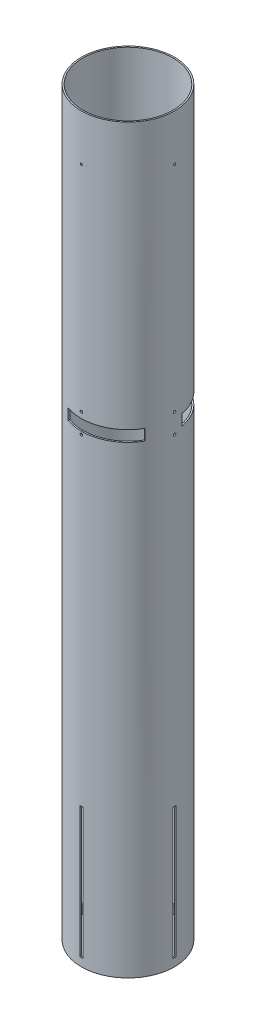
SolidWorks part; units mm, degrees
material "A-Glass Fiber"
ref_plane "Front Plane" through (0, 0, 0) normal (0, 0, 1) x (1, 0, 0)
ref_plane "Top Plane" through (0, 0, 0) normal (0, 1, 0) x (1, 0, 0)
ref_plane "Right Plane" through (0, 0, 0) normal (1, 0, 0) x (0, 0, -1)
sketch "Sketch1" plane through (0, 0, 0) normal (0, 1, 0) x (1, 0, 0)
  circle A0 centre (0, 0) radius 49.53
  circle A1 centre (0, 0) radius 51.1048
  dimension "D1" = 99.06
  dimension "D2" = 102.2096
extrude "Boss-Extrude1" add sketch "Sketch1" along normal blind 812.8
ref_plane "Plane1" through (0, 0, 0) normal (0.7071, 0, 0.7071) x (0.7071, 0, -0.7071)
ref_axis "Axis1" through (0, 812.8, 0) along (0, -1, 0)
sketch "Sketch2" plane through (0, 0, 0) normal (1, 0, 0) x (0, 0, -1)
  line L0 (0, 0) -> (0, 8.89)
  line L1 (1.5875, 8.89) -> (-1.5875, 8.89)
  line L2 (1.5875, 8.89) -> (1.5875, 152.4)
  line L3 (1.5875, 152.4) -> (-1.5875, 152.4)
  line L4 (-1.5875, 8.89) -> (-1.5875, 152.4)
  line L5 (1.5875, 8.89) -> (-1.5875, 152.4) construction
  line L6 (1.5875, 152.4) -> (-1.5875, 8.89) construction
  line L7 (51.1048, 812.8) -> (-51.1048, 812.8) construction
  line L8 (51.1048, 812.8) -> (-51.1048, 812.8)
  line L9 (0, 812.8) -> (0, 527.05)
  line L10 (-51.1048, 0) -> (51.1048, 0) construction
  circle A0 centre (0, 527.05) radius 1.3525
  point P0 (0, 80.645)
  dimension "D4" = 2.7051
  dimension "D1" = 3.175
  dimension "D5" = 527.05
  dimension "D3" = 152.4
  dimension "D2" = 8.89
extrude "Cut-Extrude1" cut sketch "Sketch2" against normal through all contours L4 L1 L2 L3 region at (0, 80.645, 0)
pattern_circular "CirPattern1" count 4 over 360 about axis through (0, 0, 0) along (0, 1, 0) of "Cut-Extrude1" reverse direction yes
extrude "Cut-Extrude2" cut sketch "Sketch2<3>" against normal through all contours A0 region at (0, 526.1207, 0.9293)
sketch "Sketch2<3>" plane through (0, 0, 0) normal (1, 0, 0) x (0, 0, -1) same geometry as "Sketch2"
pattern_circular "CirPattern2" count 4 over 360 about axis through (0, 812.8, 0) along (0, -1, 0) of "Cut-Extrude2"
sketch "Sketch3" plane through (0, 0, 0) normal (0.7071, 0, 0.7071) x (0.7071, 0, -0.7071)
  line L0 (0, 0) -> (0, 127) construction
  circle A0 centre (0, 127) radius 3.175
  dimension "D1" = 6.35
  dimension "D2" = 127
extrude "Cut-Extrude3" cut sketch "Sketch3" against normal through all
sketch "Sketch7" plane through (0, 0, 0) normal (0, 1, 0) x (1, 0, 0)
  line L0 (0, 0) -> (-44.2581, -25.5524)
  line L1 (0, 0) -> (0, 93.232) construction
  line L2 (0, 0) -> (-32.8495, 39.1485)
  line L3 (-51.1048, 0) -> (0, 0) construction
  arc A0 (-51.0869, 1.3525) -> (-51.0869, -1.3525) centre (0, 0) ccw construction
  circle A1 centre (0, 0) radius 49.53 construction
  circle A2 centre (0, 0) radius 51.1048
  circle A3 centre (0, 0) radius 51.1048
  circle A4 centre (0, 0) radius 49.53
  circle A5 centre (0, 0) radius 51.1048 construction
  arc A6 (1.3526, 51.0869) -> (-1.3525, 51.0869) centre (0, 0) ccw construction
  arc A7 (-51.0869, 1.3525) -> (-51.0869, -1.3525) centre (0, 0) ccw
  arc A8 (1.3526, 51.0869) -> (-1.3525, 51.0869) centre (0, 0) ccw
  dimension "D1" = 80
  dimension "D3" = 30
  dimension "D2" = 0
extrude "Cut-Extrude4" cut sketch "Sketch7" against normal blind 12.065 from offset 520.7 contours A4 A3 L0 region at (-43.9137, 0, 24.5741)
pattern_circular "CirPattern3" count 3 over 360 about axis through (0, 812.8, 0) along (0, -1, 0) of "Cut-Extrude4"
pattern_linear "LPattern1" count 2 spacing 21.6916 along (0, -1, 0) of "CirPattern2"
sketch "Sketch8" plane through (0, 0, 0) normal (0, 0, 1) x (1, 0, 0)
  line L0 (49.53, 812.8) -> (-49.53, 812.8) construction
  circle A0 centre (0, 762) radius 1.0922
  dimension "D1" = 2.1844
  dimension "D2" = 50.8
extrude "Cut-Extrude5" cut sketch "Sketch8" against normal through all
pattern_circular "CirPattern4" count 4 over 360 about axis through (0, 812.8, 0) along (0, -1, 0) of "Cut-Extrude5"
sketch "Sketch9" plane through (0, 0, 0) normal (0, 0, 1) x (1, 0, 0)
  line L0 (51.1048, 812.8) -> (-51.1048, 812.8) construction
  point P0 (0, 752.856)
  dimension "D1" = 59.944
hole_wizard "1/2 Clearance Hole4" positions "Sketch17" profile "Sketch18" hole size "1/2" standard "ANSI Inch" end condition through all
sketch "Sketch17" plane through (0, 0, 0) normal (0, 0, 1) x (1, 0, 0)
  point P0 (0, 752.856)
sketch "Sketch18" plane through (0, 752.856, 0) normal (1, 0, 0) x (0, -1, 0)
  line L0 (0, 0) -> (0, 51.1048)
  line L1 (0, 51.1048) -> (6.5481, 51.1048)
  line L2 (6.5481, 51.1048) -> (6.5481, 0)
  line L5 (6.5481, 0) -> (0, 0)
  line L11 (0, -6.35) -> (0, 107.95) construction
  dimension "Thru Hole Dia." = 13.0962
  dimension "Thru Hole Depth" = 51.1048
equation "\"D1@Boss-Extrude1\" = \"Aft_Section_Length\""
equation "\"AB_Coupler_OD_Length\"= 1in"
equation "\"AB_Coupling_Section_Length\"= 0.375in"
equation "\"AB_Coupler_Length\"= \"AB_Coupler_OD_Length\" + \"AB_Coupling_Section_Length\" * 2"
equation "\"AB_Coupler_Num_Screws\"= 4"
equation "\"AB_Coupling_Screw_Diameter\"= 0.1065in"
equation "\"Aft_Section_Length\" = 32in"
equation "\"D4@Sketch2\"=\"AB_Coupling_Screw_Diameter\""
equation "\"D1@CirPattern2\"=\"AB_Coupler_Num_Screws\""
equation "\"Rail_Nut_From_Bottom\"= 5in"
equation "\"Rail_Nut_Diam\"= 0.25in"
equation "\"D1@Sketch3\"=\"Rail_Nut_Diam\""
equation "\"D2@Sketch3\"=\"Rail_Nut_From_Bottom\""
equation "\"AB_BKHD_Thickness\"= 0.375in"
equation "\"AB_Mount_From_Bottom\"= 20.75in"
equation "\"Cutout_Angle\" = 60"
equation "\"Motor_OD\" = 54.4mm"
equation "\"Motor_Length\" = 401mm"
equation "\"Mid_Coupler_Length\" = 12in"
equation "\"AB_Paddle_Height\" = 0.375in"
equation "\"Num_Cutouts\" = 4"
equation "\"AB_Coupler_OD\"= 4.024in"
equation "\"AB_Coupler_ID\"= 3.7in"
equation "\"AB_Coupler_Surface_Diameter\"= 3.899in"
equation "\"AB_Central_Bushing_Length\" = 0.75in"
equation "\"Lead_Screw_Dist\" = 2in"
equation "\"Lead_Screw_Diam\" = 0.375in"
equation "\"Lead_Screw_Length\" = \"Mid_Coupler_Length\" + 2*0.375in + 2*0.5in"
equation "\"Paddle_Pin_Offset\" = 0.25in"
equation "\"Paddle_Pin_Radius\" = 2.25*2/3in"
equation "\"Paddle_Gear_OD\" = 3.2in"
equation "\"Fwd_BKHD_From_Top\" = 18in"
equation "\"Body_Tube_OD\"= 4.024in"
equation "\"Body_Tube_ID\"= 3.90in"
equation "\"Coupler_OD\" = 3.899in"
equation "\"Coupler_ID\" = 3.755in"
equation "\"Fwd_Section_Length\" = 20in"
equation "\"Mid_Section_Length\" = 4in"
equation "\"Aft_Upper_Tube_Length\" = 10in"
equation "\"Aft_Lower_Tube_Length\" = 18in"
equation "\"Nosecone_Coupler_Length\" = 5in"
equation "\"Avionics_Bulkhead_Thickness\" = 0.25in"
equation "\"Avionics_Bulkhead_Lip\" = 0.125in"
equation "\"Avionics_Board_Length\" = \"Mid_Coupler_Length\" - 2*\"Avionics_Bulkhead_Lip\""
equation "\"Lead_Screw_Hole_Diam\" = 0.386in"
equation "\"Centering_Ring_Cutout_Dia\"= 1in"
equation "\"D2@Sketch1\"=\"Body_Tube_OD\""
equation "\"D1@Sketch1\"=\"Body_Tube_ID\""
equation "\"D5@Sketch2\"=\"AB_Mount_From_Bottom\""
equation "\"D19@Cut-Extrude4\"=\"AB_Mount_From_Bottom\"-0.25"
